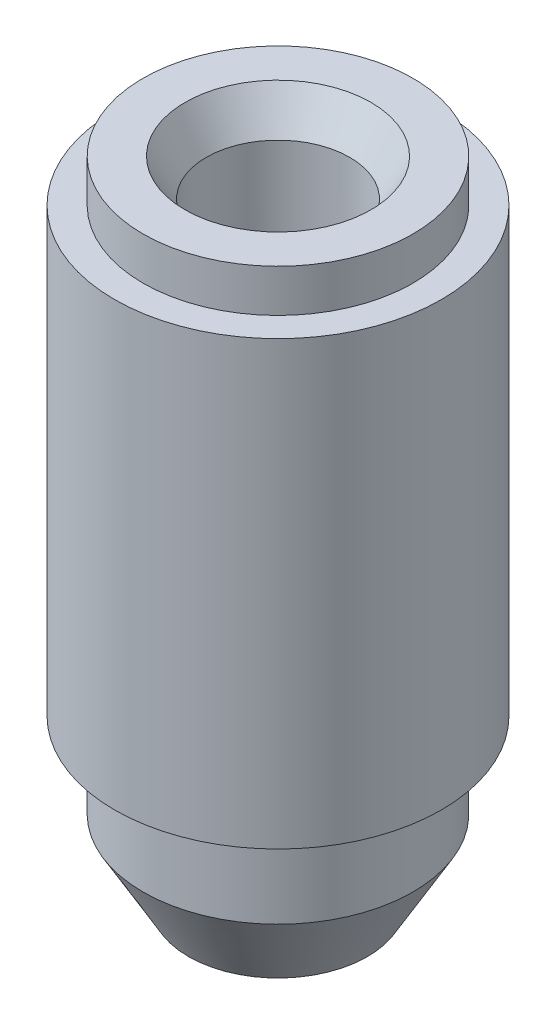
SolidWorks part; units mm, degrees
ref_plane "Front Plane" through (0, 0, 0) normal (0, 0, 1) x (1, 0, 0)
ref_plane "Top Plane" through (0, 0, 0) normal (0, 1, 0) x (1, 0, 0)
ref_plane "Right Plane" through (0, 0, 0) normal (1, 0, 0) x (0, 0, -1)
sketch "Sketch1" plane through (0, 0, 0) normal (0, 0, 1) x (1, 0, 0)
  line L0 (5.05, -18.56) -> (5.05, 18.56)
  line L1 (5.05, 18.56) -> (9.5, 18.56)
  line L2 (9.5, 18.56) -> (9.5, 15.56)
  line L3 (9.5, 15.56) -> (11.5, 15.56)
  line L4 (11.5, 15.56) -> (11.5, -15.56)
  line L5 (12, 0) -> (5, 0) construction
  line L6 (0, 19.5332) -> (0, 0) construction
  line L7 (9.5, -15.56) -> (11.5, -15.56)
  line L8 (9.5, -18.56) -> (9.5, -15.56)
  line L9 (5.05, -18.56) -> (9.5, -18.56) construction
  line L10 (5.05, -18.56) -> (5.05, -27.1026)
  line L11 (5.05, -27.1026) -> (6.3, -27.1026)
  line L12 (6.3, -27.1026) -> (9.5, -21.56)
  line L13 (9.5, -21.56) -> (9.5, -18.56)
  point P18 (9.5, -17.06)
  dimension "D1" = 5.05
  dimension "D2" = 15.56
  dimension "D3" = 11.5
  dimension "D4" = 2
  dimension "D5" = 3
  dimension "D6" = 1.25
  dimension "D7" = 3
  dimension "D8" = 30
  dimension "D9" = 5.5426
revolve "Revolve1" add sketch "Sketch1" angle 360 about L6
ref_axis "Axis1" through (0, -27.1026, 0) along (0, 1, 0)
chamfer "Chamfer1" distance 1.5 angle 60 1 edges at (0, 18.56, 5.05) first distance on face at (0, 18.56, 5.05)
